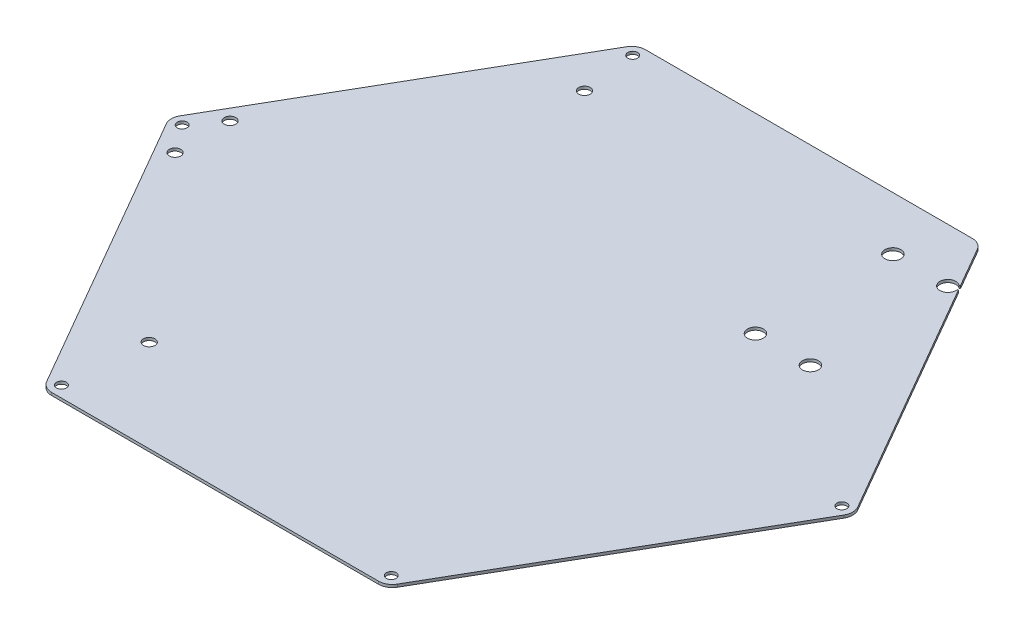
SolidWorks part; units mm, degrees
material "Thornel Mat VMA"
ref_plane "Front Plane" through (0, 0, 0) normal (0, 0, 1) x (1, 0, 0)
ref_plane "Top Plane" through (0, 0, 0) normal (0, 1, 0) x (1, 0, 0)
ref_plane "Right Plane" through (0, 0, 0) normal (1, 0, 0) x (0, 0, -1)
sketch "Sketch1" plane through (0, 0, 0) normal (0, 1, 0) x (1, 0, 0)
  line L1 (62.3538, 0) -> (187.0615, 0)
  line L2 (187.0615, 0) -> (249.4153, 108)
  line L3 (249.4153, 108) -> (187.0615, 216)
  line L4 (187.0615, 216) -> (62.3538, 216)
  line L5 (62.3538, 216) -> (0, 108)
  line L6 (0, 108) -> (62.3538, 0)
  circle A0 centre (124.7077, 108) radius 108 construction
  dimension "D1" = 216
extrude "Boss-Extrude1" add sketch "Sketch1" along normal blind 1
fillet "Fillet1" radius 5 6 edges at (0, 0.5, -108) (62.3538, 0.5, -216) (187.0615, 0.5, -216) (249.4153, 0.5, -108) (62.3538, 0.5, 0) (187.0615, 0.5, 0)
sketch "Sketch2" plane through (0, 1, 0) normal (0, 1, 0) x (1, 0, 0)
  line L0 (124.7077, 0) -> (124.7077, 216) construction
  line L1 (65.2406, 0) -> (184.1747, 0) construction
  line L2 (184.1747, 216) -> (65.2406, 216) construction
  line L3 (124.7077, 108) -> (244.7077, 108) construction
  line L4 (174.7077, 196.57) -> (194.7077, 196.57)
  line L5 (174.7077, 196.57) -> (174.7077, 146.57)
  line L6 (174.7077, 146.57) -> (194.7077, 146.57)
  line L7 (194.7077, 196.57) -> (194.7077, 146.57)
  line L8 (174.7077, 196.57) -> (194.7077, 146.57) construction
  line L9 (174.7077, 146.57) -> (194.7077, 196.57) construction
  line L10 (124.7077, 108) -> (64.7077, 211.923) construction
  line L11 (124.7077, 108) -> (4.7077, 108) construction
  line L12 (124.7077, 108) -> (64.7077, 4.077) construction
  line L13 (124.7077, 108) -> (184.7077, 4.077) construction
  point P6 (184.7077, 171.57)
  dimension "D1" = 50
  dimension "D2" = 20
  dimension "D3" = 50
  dimension "D4" = 38.57
  dimension "D5" = 120
  dimension "D6" = 60
  dimension "D7" = 60
hole_wizard "M5 Clearance Hole1" positions "Sketch4" profile "Sketch5" hole size "M5" standard "ANSI Metric"
sketch "Sketch4" plane through (0, 1, 0) normal (0, 1, 0) x (1, 0, 0)
  point P0 (174.7077, 146.57)
  point P3 (194.7077, 146.57)
  point P6 (194.7077, 196.57)
  point P9 (174.7077, 196.57)
sketch "Sketch5" plane through (174.7077, 1, -146.57) normal (1, 0, 0) x (0, 0, 1)
  line L0 (0, 0) -> (0, 6.7425)
  line L1 (0, 6.7425) -> (2.9, 5)
  line L2 (2.9, 5) -> (2.9, 0)
  line L5 (2.9, 0) -> (0, 0)
  line L10 (0, 6.7425) -> (-2.9, 5) construction
  line L11 (0, -6.35) -> (0, 107.95) construction
  dimension "Hole Dia." = 5.8
  dimension "Hole Depth" = 5
  dimension "Drill Angle" = 118
hole_wizard "M3 Clearance Hole1" positions "Sketch7" profile "Sketch8" hole size "M3" standard "ANSI Metric" end condition through all
sketch "Sketch7" plane through (0, 1, 0) normal (0, 1, 0) x (1, 0, 0)
  point P0 (4.7077, 108)
  point P3 (64.7077, 211.923)
  point P6 (244.7077, 108)
  point P9 (184.7077, 4.077)
  point P12 (64.7077, 4.077)
sketch "Sketch8" plane through (4.7077, 1, -108) normal (1, 0, 0) x (0, 0, 1)
  line L0 (0, 0) -> (0, 1)
  line L1 (0, 1) -> (1.8, 1)
  line L2 (1.8, 1) -> (1.8, 0)
  line L5 (1.8, 0) -> (0, 0)
  line L11 (0, -6.35) -> (0, 107.95) construction
  dimension "Thru Hole Dia." = 3.6
  dimension "Thru Hole Depth" = 1
sketch "Sketch9" plane through (0, 1, 0) normal (0, 1, 0) x (1, 0, 0)
  line L0 (196.564, 198.798) -> (196.8858, 198.9838)
  line L1 (247.9719, 110.5) -> (188.5049, 213.5) construction
  line L2 (197.5653, 197.0637) -> (197.8871, 197.2495)
  line L3 (196.8858, 198.9838) -> (197.8871, 197.2495)
  line L4 (196.564, 198.798) -> (197.5653, 197.0637)
  circle A0 centre (194.7077, 196.57) radius 2.9 construction
extrude "Cut-Extrude1" cut sketch "Sketch9" against normal through all
sketch "Sketch10" plane through (0, 1, 0) normal (0, 1, 0) x (1, 0, 0)
  line L0 (54.8255, 191.9605) -> (67.1244, 191.9605) construction
  line L1 (67.1244, 191.9605) -> (67.1244, 33.5901) construction
  line L2 (67.1244, 33.5901) -> (49.3115, 33.5901) construction
  line L3 (54.8255, 191.9605) -> (12.1244, 118) construction
  line L4 (49.3115, 33.5901) -> (12.1244, 98) construction
  line L5 (12.1244, 98) -> (12.1244, 118) construction
  line L6 (4.7077, 108) -> (12.1244, 108) construction
  line L7 (60.9105, 213.5) -> (1.4434, 110.5) construction
  line L8 (1.4434, 105.5) -> (60.9105, 2.5) construction
  circle A1 centre (12.1244, 118) radius 2.1
  circle A2 centre (12.1244, 98) radius 2.1
  circle A3 centre (67.1244, 33.5901) radius 2.1
  circle A4 centre (67.1244, 191.9605) radius 2.1
  dimension "D1" = 55
  dimension "D2" = 4.2
  dimension "D3" = 20
  dimension "D4" = 5.5
extrude "Cut-Extrude2" cut sketch "Sketch10" against normal through all
